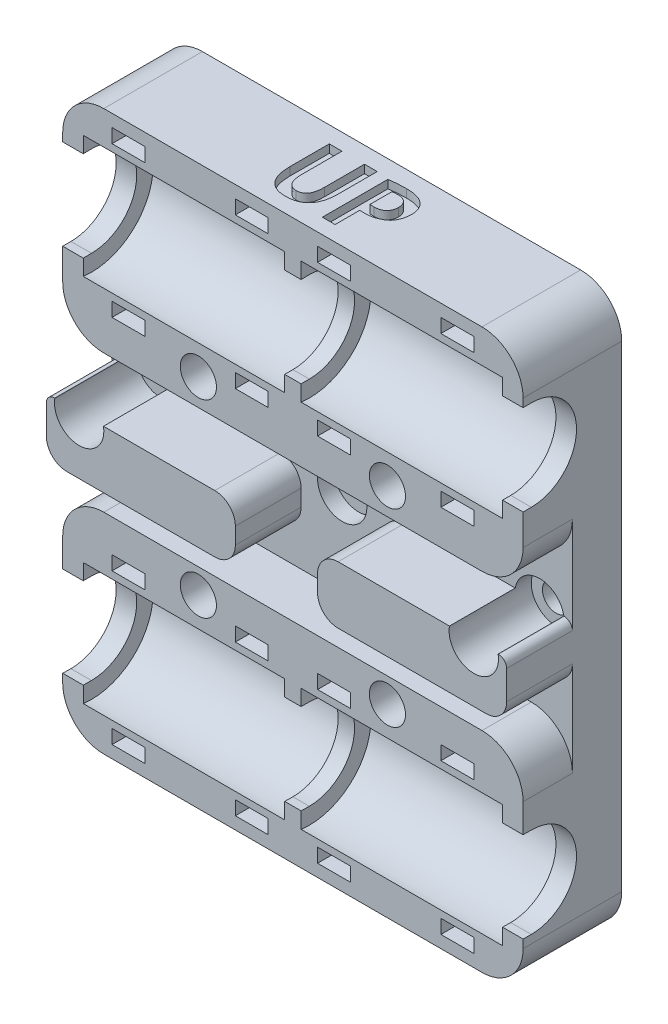
SolidWorks part; units mm, degrees
material "ABS generico"
ref_plane "Front Plane" through (0, 0, 0) normal (0, 0, 1) x (1, 0, 0)
ref_plane "Top Plane" through (0, 0, 0) normal (0, 1, 0) x (1, 0, 0)
ref_plane "Right Plane" through (0, 0, 0) normal (1, 0, 0) x (0, 0, -1)
sketch "Sketch1" plane through (0, 0, 0) normal (1, 0, 0) x (0, 0, -1)
  line L0 (2, 28) -> (3, 28) construction
  line L1 (3, 28) -> (4.4235, 27.8126) construction
  line L2 (4.4235, 27.8126) -> (5.75, 27.2631) construction
  line L3 (5.75, 27.2631) -> (6.8891, 26.3891) construction
  line L4 (6.8891, 26.3891) -> (7.7631, 25.25) construction
  line L5 (7.7631, 25.25) -> (8.3126, 23.9235) construction
  line L6 (8.3126, 23.9235) -> (8.5, 22.5) construction
  line L7 (8.5, 22.5) -> (8.3126, 21.0765) construction
  line L8 (8.3126, 21.0765) -> (7.7631, 19.75) construction
  line L9 (7.7631, 19.75) -> (6.8891, 18.6109) construction
  line L10 (6.8891, 18.6109) -> (5.75, 17.7369) construction
  line L11 (5.75, 17.7369) -> (4.4235, 17.1874) construction
  line L12 (3, 17) -> (4.4235, 17.1874) construction
  line L13 (2, 17) -> (3, 17) construction
  line L14 (2, -17) -> (3, -17) construction
  line L15 (3, -17) -> (4.4235, -17.1874) construction
  line L16 (4.4235, -17.1874) -> (5.75, -17.7369) construction
  line L17 (5.75, -17.7369) -> (6.8891, -18.6109) construction
  line L18 (6.8891, -18.6109) -> (7.7631, -19.75) construction
  line L19 (7.7631, -19.75) -> (8.3126, -21.0765) construction
  line L20 (8.3126, -21.0765) -> (8.5, -22.5) construction
  line L21 (8.5, -22.5) -> (8.3126, -23.9235) construction
  line L22 (8.3126, -23.9235) -> (7.7631, -25.25) construction
  line L23 (7.7631, -25.25) -> (6.8891, -26.3891) construction
  line L24 (6.8891, -26.3891) -> (5.75, -27.2631) construction
  line L25 (5.75, -27.2631) -> (4.4235, -27.8126) construction
  line L26 (4.4235, -27.8126) -> (3, -28) construction
  line L27 (3, -28) -> (2, -28) construction
  line L28 (-19.5101, 0) -> (53.4154, 0) construction
  line L29 (3, 22.5) -> (3, -22.5391) construction
  line L30 (2, 34) -> (2, -34) construction
  line L31 (14, 34) -> (14, -34) construction
  line L32 (2, -34) -> (14, -34) construction
  line L33 (2, 34) -> (14, 34) construction
  line L34 (14, 28) -> (14, -28) construction
  line L35 (2, 28) -> (2, -28) construction
  line L36 (-19.5101, 34) -> (53.4154, 34) construction
  line L37 (-19.5101, -34) -> (53.4154, -34) construction
  line L38 (2, 8.25) -> (14, 8.25) construction
  line L39 (2, -8.25) -> (14, -8.25) construction
  line L40 (8, 34) -> (8, -34) construction
  line L41 (0, 2.5) -> (8, 2.5) construction
  line L42 (0, -7) -> (8, -7) construction
  line L43 (2, 2.5) -> (14, 2.5) construction
  line L44 (2, -7) -> (14, -7) construction
  line L45 (0, 2.5) -> (0, -7) construction
  line L46 (0, 34) -> (0, -34) construction
  circle A0 centre (3, 22.5) radius 7.5 construction
  circle A1 centre (3, -22.5) radius 7.5 construction
  circle A2 centre (3, 22.5) radius 5.5 construction
  circle A3 centre (3, -22.5) radius 5.5 construction
  dimension "D1" = 15
  dimension "D2" = 11
  dimension "D12" = 22.5
  dimension "D3" = 12
  dimension "D4" = 34
  dimension "D5" = 34
  dimension "D6" = 25.75
  dimension "D7" = 25.75
  dimension "D8" = 6
  dimension "D9" = 5.75
  dimension "D10" = 9.5
  dimension "D11" = 8
sketch "Sketch2" plane through (0, 0, 0) normal (0, 0, 1) x (1, 0, 0)
  line L0 (-28, 0) -> (28, 0) construction
  line L1 (-28, 22.5) -> (28, 22.5) construction
  line L2 (-28, -22.5) -> (28, -22.5) construction
  dimension "D1" = 56
  dimension "D2" = 22.5
  dimension "D3" = 22.5
sketch "Sketch3" plane through (0, 0, 0) normal (1, 0, 0) x (0, 0, -1)
  line L1 (14, 34) -> (8, 34)
  line L2 (14, 34) -> (14, -34)
  line L3 (14, -34) -> (8, -34)
  line L4 (8, 34) -> (8, -34)
extrude "Extrude1" add sketch "Sketch3" along normal blind 28 and the other way blind 28
sketch "Sketch4" plane through (0, 0, 0) normal (1, 0, 0) x (0, 0, -1)
  line L0 (-17.6716, 0) -> (32.3469, 0) construction
  line L2 (2, -8.5182) -> (2, -34)
  line L3 (2, -34) -> (8, -34)
  line L4 (8, -8.5182) -> (8, -34)
  line L5 (-19.5101, 0) -> (53.4154, 0) construction
  line L6 (2, 34) -> (8, 34)
  line L7 (8, 8.25) -> (8, 34)
  line L8 (2, 8.25) -> (2, 34)
  line L9 (2, 8.25) -> (8, 8.25)
  line L10 (8, -8.5182) -> (2, -8.5182)
extrude "Extrude2" add sketch "Sketch4" along normal blind 28 and the other way blind 28
ref_plane "Plane1" through (25.5, 0, 0) normal (1, 0, 0) x (0, 0, -1)
ref_plane "Plane2" through (1, 0, 0) normal (1, 0, 0) x (0, 0, -1)
sketch "Sketch5" plane through (25.5, 0, 0) normal (1, 0, 0) x (0, 0, -1)
  line L0 (3, 28) -> (-0.9437, 27.936)
  line L1 (3, 17) -> (-0.7662, 17)
  line L2 (-0.9437, 27.936) -> (-0.7662, 17)
  line L3 (-19.5101, 0) -> (30.5697, 0) construction
  line L4 (-19.5101, 0) -> (53.4154, 0) construction
  line L5 (-0.9437, -27.936) -> (-0.7662, -17)
  line L6 (3, -17) -> (-0.7662, -17)
  line L7 (3, -28) -> (-0.9437, -27.936)
  arc A0 (3, 17) -> (2.8215, 27.9971) centre (3, 22.5) ccw
  arc A1 (3, -17) -> (2.8215, -27.9971) centre (3, -22.5) cw
  dimension "D1" = 11
extrude "Extrude3" cut sketch "Sketch5" against normal blind 55 and the other way blind 4 contours L1 A0 L0 L2 | A1 L6 L5 L7 region at (25.5, 22.5123, -3.3283) region at (25.5, -22.5123, -3.3283)
ref_plane "Plane3" through (-1, 0, 0) normal (1, 0, 0) x (0, 0, -1)
sketch "Sketch6" plane through (1, 0, 0) normal (1, 0, 0) x (0, 0, -1)
  line L0 (-13.9491, 0) -> (21.386, 0) construction
  line L1 (-19.5101, 0) -> (53.4154, 0) construction
  circle A0 centre (3, 22.5) radius 7.5
  circle A1 centre (3, -22.5) radius 7.5
  dimension "D1" = 15
extrude "Extrude4" cut sketch "Sketch6" along normal blind 24.5
sketch "Sketch7" plane through (-1, 0, 0) normal (1, 0, 0) x (0, 0, -1)
  line L0 (-8.9355, 0) -> (16.9527, 0) construction
  line L1 (-19.5101, 0) -> (53.4154, 0) construction
  circle A0 centre (3, 22.5) radius 7.5
  circle A1 centre (3, -22.5) radius 7.5
  dimension "D1" = 15
extrude "Extrude5" cut sketch "Sketch7" against normal blind 24.5
sketch "Sketch8" plane through (0, 0, -8) normal (0, 0, 1) x (1, 0, 0)
  line L0 (5, 2.5103) -> (28, 2.5103)
  line L2 (5, -4.4897) -> (28, -4.4897)
  line L3 (28, -4.4897) -> (28, 2.5103)
  line L5 (0, 2.5103) -> (30.6268, 2.5103) construction
  line L6 (0, -4.4897) -> (30.6268, -4.4897) construction
  line L7 (5, -4.4897) -> (5, 2.5103)
  line L8 (0, 45.3075) -> (0, -47.4003) construction
  line L9 (-5, -4.4897) -> (-5, 2.5103)
  line L10 (-28, -4.4897) -> (-28, 2.5103)
  line L11 (-5, -4.4897) -> (-28, -4.4897)
  line L12 (-5, 2.5103) -> (-28, 2.5103)
  dimension "D1" = 7
  dimension "D2" = 23
extrude "Extrude6" add sketch "Sketch8" along normal blind 8
sketch "Sketch9" plane through (0, 0, 0) normal (0, 0, 1) x (1, 0, 0)
  line L2 (-11.5, -11.5) -> (11.5, -11.5) construction
  line L5 (11.5, 11.5) -> (11.5, -11.5) construction
  line L6 (11.5, 11.5) -> (-11.5, 11.5) construction
  line L7 (0, 0) -> (43.4325, 0) construction
  line L8 (0, 0) -> (0, 41.5295) construction
  circle A6 centre (-11.5, 11.5) radius 2.2
  circle A7 centre (-11.5, -11.5) radius 2.2
  circle A8 centre (11.5, -11.5) radius 2.2
  circle A9 centre (11.5, 11.5) radius 2.2
  dimension "D1" = 4.4
  dimension "D2" = 11.5
  dimension "D3" = 11.5
extrude "Extrude7" cut sketch "Sketch9" against normal blind 14 contours A6 | A9 | A8 | A7
sketch "Sketch10" plane through (0, 0, 0) normal (0, 0, 1) x (1, 0, 0)
  circle A0 centre (0, 2) radius 1.65
  circle A2 centre (24, 2) radius 1.65
  circle A3 centre (-24, 2) radius 1.65
  dimension "D1" = 3.3
  dimension "D2" = 2
  dimension "D3" = 2
extrude "Extrude8" cut sketch "Sketch10" against normal blind 14
sketch "Sketch11" plane through (0, 0, 0) normal (0, 0, 1) x (1, 0, 0)
  circle A0 centre (0, 2) radius 3
  circle A1 centre (24, 2) radius 3
  circle A2 centre (-24, 2) radius 3
  dimension "D1" = 6
  dimension "D2" = 2
  dimension "D3" = 2
extrude "Extrude9" cut sketch "Sketch11" against normal blind 10
sketch "Sketch12" plane through (0, 0, -14) normal (0, 0, -1) x (-1, 0, 0)
  line L0 (0, 53.1914) -> (0, 0) construction
  line L1 (-54.1669, 0) -> (0, 0) construction
  line L2 (28, 34) -> (-28, 34) construction
  line L3 (-3, 32.5) -> (-7, 32.5)
  line L4 (-3, 32.5) -> (-3, 12.5)
  line L5 (-3, 12.5) -> (-7, 12.5)
  line L6 (-7, 32.5) -> (-7, 12.5)
  line L7 (-18, 32.5) -> (-22, 32.5)
  line L8 (-22, 32.5) -> (-22, 12.5)
  line L9 (-18, 32.5) -> (-18, 12.5)
  line L10 (-18, 12.5) -> (-22, 12.5)
  line L11 (18, 12.5) -> (22, 12.5)
  line L12 (18, 32.5) -> (18, 12.5)
  line L13 (22, 32.5) -> (22, 12.5)
  line L14 (18, 32.5) -> (22, 32.5)
  line L15 (7, 32.5) -> (7, 12.5)
  line L16 (3, 12.5) -> (7, 12.5)
  line L17 (3, 32.5) -> (3, 12.5)
  line L18 (3, 32.5) -> (7, 32.5)
  line L19 (3, -32.5) -> (7, -32.5)
  line L20 (3, -32.5) -> (3, -12.5)
  line L21 (3, -12.5) -> (7, -12.5)
  line L22 (7, -32.5) -> (7, -12.5)
  line L23 (18, -32.5) -> (22, -32.5)
  line L24 (22, -32.5) -> (22, -12.5)
  line L25 (18, -32.5) -> (18, -12.5)
  line L26 (18, -12.5) -> (22, -12.5)
  line L27 (-18, -12.5) -> (-22, -12.5)
  line L28 (-18, -32.5) -> (-18, -12.5)
  line L29 (-22, -32.5) -> (-22, -12.5)
  line L30 (-18, -32.5) -> (-22, -32.5)
  line L31 (-7, -32.5) -> (-7, -12.5)
  line L32 (-3, -12.5) -> (-7, -12.5)
  line L33 (-3, -32.5) -> (-3, -12.5)
  line L34 (-3, -32.5) -> (-7, -32.5)
  dimension "D2" = 20
  dimension "D1" = 4
  dimension "D3" = 1.5
  dimension "D4" = 6
  dimension "D5" = 2
extrude "Extrude12" cut sketch "Sketch12" against normal blind 1.2
sketch "Sketch14" plane through (0, 0, -14) normal (0, 0, -1) x (-1, 0, 0)
  line L0 (-18, 12.5) -> (-18, 32.5) construction
  line L1 (-22, 32.5) -> (-18, 32.5)
  line L2 (-22, 32.5) -> (-22, 30.8)
  line L3 (-22, 30.8) -> (-18, 30.8)
  line L4 (-18, 32.5) -> (-18, 30.8)
  line L7 (-18, 12.5) -> (-18, 14.2)
  line L8 (-22, 14.2) -> (-18, 14.2)
  line L9 (-22, 12.5) -> (-22, 14.2)
  line L10 (-22, 12.5) -> (-18, 12.5)
  line L11 (-7, 32.5) -> (-3, 32.5)
  line L12 (-7, 32.5) -> (-7, 30.8)
  line L13 (-7, 30.8) -> (-3, 30.8)
  line L14 (-3, 32.5) -> (-3, 30.8)
  line L15 (-3, 12.5) -> (-3, 14.2)
  line L16 (-7, 14.2) -> (-3, 14.2)
  line L17 (-7, 12.5) -> (-3, 12.5)
  line L18 (-7, 12.5) -> (-7, 14.2)
  line L21 (7, 12.5) -> (7, 14.2)
  line L22 (7, 12.5) -> (3, 12.5)
  line L23 (7, 14.2) -> (3, 14.2)
  line L24 (3, 12.5) -> (3, 14.2)
  line L25 (3, 32.5) -> (3, 30.8)
  line L26 (7, 30.8) -> (3, 30.8)
  line L27 (7, 32.5) -> (7, 30.8)
  line L28 (7, 32.5) -> (3, 32.5)
  line L29 (22, 12.5) -> (18, 12.5)
  line L30 (22, 12.5) -> (22, 14.2)
  line L31 (22, 14.2) -> (18, 14.2)
  line L32 (18, 12.5) -> (18, 14.2)
  line L33 (18, 32.5) -> (18, 30.8)
  line L34 (22, 30.8) -> (18, 30.8)
  line L35 (22, 32.5) -> (22, 30.8)
  line L36 (22, 32.5) -> (18, 32.5)
  line L38 (22, -32.5) -> (18, -32.5)
  line L39 (22, -32.5) -> (22, -30.8)
  line L40 (22, -30.8) -> (18, -30.8)
  line L41 (18, -32.5) -> (18, -30.8)
  line L42 (18, -12.5) -> (18, -14.2)
  line L43 (22, -14.2) -> (18, -14.2)
  line L44 (22, -12.5) -> (22, -14.2)
  line L45 (22, -12.5) -> (18, -12.5)
  line L46 (7, -32.5) -> (3, -32.5)
  line L47 (7, -32.5) -> (7, -30.8)
  line L48 (7, -30.8) -> (3, -30.8)
  line L49 (3, -32.5) -> (3, -30.8)
  line L50 (3, -12.5) -> (3, -14.2)
  line L51 (7, -14.2) -> (3, -14.2)
  line L52 (7, -12.5) -> (3, -12.5)
  line L53 (7, -12.5) -> (7, -14.2)
  line L54 (-7, -12.5) -> (-7, -14.2)
  line L55 (-7, -12.5) -> (-3, -12.5)
  line L56 (-7, -14.2) -> (-3, -14.2)
  line L57 (-3, -12.5) -> (-3, -14.2)
  line L58 (-3, -32.5) -> (-3, -30.8)
  line L59 (-7, -30.8) -> (-3, -30.8)
  line L60 (-7, -32.5) -> (-7, -30.8)
  line L61 (-7, -32.5) -> (-3, -32.5)
  line L62 (-22, -12.5) -> (-18, -12.5)
  line L63 (-22, -12.5) -> (-22, -14.2)
  line L64 (-22, -14.2) -> (-18, -14.2)
  line L65 (-18, -12.5) -> (-18, -14.2)
  line L66 (-18, -32.5) -> (-18, -30.8)
  line L67 (-22, -30.8) -> (-18, -30.8)
  line L68 (-22, -32.5) -> (-22, -30.8)
  line L69 (-22, -32.5) -> (-18, -32.5)
  dimension "D1" = 1.7
  dimension "D2" = 2
extrude "Extrude13" cut sketch "Sketch14" against normal blind 12
fillet "Fillet1" radius 5 4 edges at (28, 34, -8) (28, -34, -8) (-28, -34, -8) (-28, 34, -8)
fillet "Fillet2" radius 5 4 edges at (28, 8.25, -5) (-28, 8.25, -5)
fillet "Fillet3" radius 2.5 6 edges at (28, -4.4897, -4) (-28, -4.4897, -4) (5, -4.4897, -4) (5, 2.5103, -4) (-5, -4.4897, -4) (-5, 2.5103, -4)
fillet "Fillet4" radius 1 2 edges at (28, 2.5103, -4) (-28, 2.5103, -4)
fillet "Fillet5" radius 3 16 edges at (-20, -30.8, -12.8) (-5, -30.8, -12.8) (5, -30.8, -12.8) (20, -30.8, -12.8) (20, -14.2, -12.8) (5, -14.2, -12.8) (-5, -14.2, -12.8) (-20, -14.2, -12.8) (-20, 30.8, -12.8) (-20, 14.2, -12.8) (-5, 14.2, -12.8) (-5, 30.8, -12.8) (5, 30.8, -12.8) (5, 14.2, -12.8) (20, 14.2, -12.8) (20, 30.8, -12.8)
fillet "Fillet7" radius 2 8 edges at (20, 12.5, -14) (5, 12.5, -14) (-5, 12.5, -14) (-20, 12.5, -14) (-20, -12.5, -14) (-5, -12.5, -14) (5, -12.5, -14) (20, -12.5, -14)
sketch "Sketch15" plane through (0, 34, 0) normal (0, 1, 0) x (1, 0, 0)
  text T0 "UP" font "@Adobe Gothic Std B" height in points 26
extrude "Extrude14" cut sketch "Sketch15" against normal blind 1
